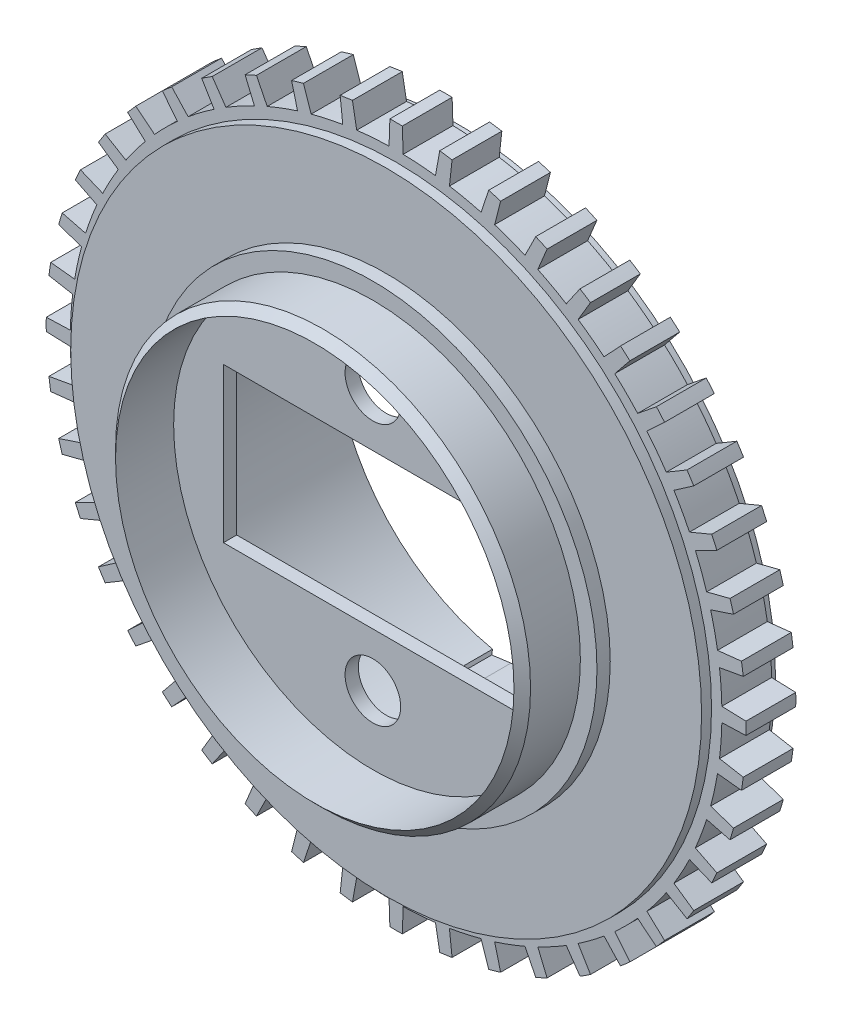
SolidWorks part; units mm, degrees
material "ABS"
ref_plane "Alzado" through (0, 0, 0) normal (0, 0, 1) x (1, 0, 0)
ref_plane "Planta" through (0, 0, 0) normal (0, 1, 0) x (1, 0, 0)
ref_plane "Vista lateral" through (0, 0, 0) normal (1, 0, 0) x (0, 0, -1)
sketch "Croquis1" plane through (0, 0, 0) normal (0, 0, 1) x (1, 0, 0)
  line L0 (0, 0) -> (0, 14.5885) construction
  line L1 (-0.375, 21.0712) -> (-0.425, 19.62)
  line L2 (0.375, 21.0712) -> (0.425, 19.62)
  line L3 (3.3699, 20.8034) -> (3.2129, 19.3598)
  line L4 (2.6276, 20.9101) -> (2.3715, 19.4807)
  line L5 (6.2963, 20.112) -> (5.9354, 18.7055)
  line L6 (5.5766, 20.3233) -> (5.1198, 18.9449)
  line L7 (9.0944, 19.0113) -> (8.537, 17.6704)
  line L8 (8.4122, 19.3228) -> (7.7638, 18.0235)
  line L9 (11.7074, 17.5235) -> (10.9649, 16.2756)
  line L10 (11.0765, 17.929) -> (10.2498, 16.7351)
  line L11 (14.0821, 15.679) -> (13.1695, 14.5495)
  line L12 (13.5153, 16.1701) -> (12.5271, 15.1061)
  line L13 (16.1701, 13.5153) -> (15.1061, 12.5271)
  line L14 (15.679, 14.0821) -> (14.5495, 13.1695)
  line L15 (17.929, 11.0765) -> (16.7351, 10.2498)
  line L16 (17.5235, 11.7074) -> (16.2756, 10.9649)
  line L17 (19.3228, 8.4122) -> (18.0235, 7.7638)
  line L18 (19.0113, 9.0944) -> (17.6704, 8.537)
  line L19 (20.3233, 5.5766) -> (18.9449, 5.1198)
  line L20 (20.112, 6.2963) -> (18.7055, 5.9354)
  line L21 (20.9101, 2.6276) -> (19.4807, 2.3715)
  line L22 (20.8034, 3.3699) -> (19.3598, 3.2129)
  line L23 (21.0712, -0.375) -> (19.62, -0.425)
  line L24 (21.0712, 0.375) -> (19.62, 0.425)
  line L25 (20.8034, -3.3699) -> (19.3598, -3.2129)
  line L26 (20.9101, -2.6276) -> (19.4807, -2.3715)
  line L27 (20.112, -6.2963) -> (18.7055, -5.9354)
  line L28 (20.3233, -5.5766) -> (18.9449, -5.1198)
  line L29 (19.0113, -9.0944) -> (17.6704, -8.537)
  line L30 (19.3228, -8.4122) -> (18.0235, -7.7638)
  line L31 (17.5235, -11.7074) -> (16.2756, -10.9649)
  line L32 (17.929, -11.0765) -> (16.7351, -10.2498)
  line L33 (15.679, -14.0821) -> (14.5495, -13.1695)
  line L34 (16.1701, -13.5153) -> (15.1061, -12.5271)
  line L35 (13.5153, -16.1701) -> (12.5271, -15.1061)
  line L36 (14.0821, -15.679) -> (13.1695, -14.5495)
  line L37 (11.0765, -17.929) -> (10.2498, -16.7351)
  line L38 (11.7074, -17.5235) -> (10.9649, -16.2756)
  line L39 (8.4122, -19.3228) -> (7.7638, -18.0235)
  line L40 (9.0944, -19.0113) -> (8.537, -17.6704)
  line L41 (5.5766, -20.3233) -> (5.1198, -18.9449)
  line L42 (6.2963, -20.112) -> (5.9354, -18.7055)
  line L43 (2.6276, -20.9101) -> (2.3715, -19.4807)
  line L44 (3.3699, -20.8034) -> (3.2129, -19.3598)
  line L45 (-0.375, -21.0712) -> (-0.425, -19.62)
  line L46 (0.375, -21.0712) -> (0.425, -19.62)
  line L47 (-3.3699, -20.8034) -> (-3.2129, -19.3598)
  line L48 (-2.6276, -20.9101) -> (-2.3715, -19.4807)
  line L49 (-6.2963, -20.112) -> (-5.9354, -18.7055)
  line L50 (-5.5766, -20.3233) -> (-5.1198, -18.9449)
  line L51 (-9.0944, -19.0113) -> (-8.537, -17.6704)
  line L52 (-8.4122, -19.3228) -> (-7.7638, -18.0235)
  line L53 (-11.7074, -17.5235) -> (-10.9649, -16.2756)
  line L54 (-11.0765, -17.929) -> (-10.2498, -16.7351)
  line L55 (-14.0821, -15.679) -> (-13.1695, -14.5495)
  line L56 (-13.5153, -16.1701) -> (-12.5271, -15.1061)
  line L57 (-16.1701, -13.5153) -> (-15.1061, -12.5271)
  line L58 (-15.679, -14.0821) -> (-14.5495, -13.1695)
  line L59 (-17.929, -11.0765) -> (-16.7351, -10.2498)
  line L60 (-17.5235, -11.7074) -> (-16.2756, -10.9649)
  line L61 (-19.3228, -8.4122) -> (-18.0235, -7.7638)
  line L62 (-19.0113, -9.0944) -> (-17.6704, -8.537)
  line L63 (-20.3233, -5.5766) -> (-18.9449, -5.1198)
  line L64 (-20.112, -6.2963) -> (-18.7055, -5.9354)
  line L65 (-20.9101, -2.6276) -> (-19.4807, -2.3715)
  line L66 (-20.8034, -3.3699) -> (-19.3598, -3.2129)
  line L67 (-21.0712, 0.375) -> (-19.62, 0.425)
  line L68 (-21.0712, -0.375) -> (-19.62, -0.425)
  line L69 (-20.8034, 3.3699) -> (-19.3598, 3.2129)
  line L70 (-20.9101, 2.6276) -> (-19.4807, 2.3715)
  line L71 (-20.112, 6.2963) -> (-18.7055, 5.9354)
  line L72 (-20.3233, 5.5766) -> (-18.9449, 5.1198)
  line L73 (-19.0113, 9.0944) -> (-17.6704, 8.537)
  line L74 (-19.3228, 8.4122) -> (-18.0235, 7.7638)
  line L75 (-19.3228, 8.4122) -> (-19.0113, 9.0944)
  line L76 (-17.5235, 11.7074) -> (-16.2756, 10.9649)
  line L77 (-17.929, 11.0765) -> (-16.7351, 10.2498)
  line L78 (-15.679, 14.0821) -> (-14.5495, 13.1695)
  line L79 (-16.1701, 13.5153) -> (-15.1061, 12.5271)
  line L80 (-13.5153, 16.1701) -> (-12.5271, 15.1061)
  line L81 (-14.0821, 15.679) -> (-13.1695, 14.5495)
  line L82 (-11.0765, 17.929) -> (-10.2498, 16.7351)
  line L83 (-11.7074, 17.5235) -> (-10.9649, 16.2756)
  line L84 (-8.4122, 19.3228) -> (-7.7638, 18.0235)
  line L85 (-9.0944, 19.0113) -> (-8.537, 17.6704)
  line L86 (-5.5766, 20.3233) -> (-5.1198, 18.9449)
  line L87 (-6.2963, 20.112) -> (-5.9354, 18.7055)
  line L88 (-2.6276, 20.9101) -> (-2.3715, 19.4807)
  line L89 (-3.3699, 20.8034) -> (-3.2129, 19.3598)
  line L90 (-3.3699, 20.8034) -> (-2.6276, 20.9101)
  line L91 (-6.2963, 20.112) -> (-5.5766, 20.3233)
  line L92 (-9.0944, 19.0113) -> (-8.4122, 19.3228)
  line L93 (-11.7074, 17.5235) -> (-11.0765, 17.929)
  line L94 (-14.0821, 15.679) -> (-13.5153, 16.1701)
  line L95 (-16.1701, 13.5153) -> (-15.679, 14.0821)
  line L96 (-17.929, 11.0765) -> (-17.5235, 11.7074)
  arc A0 (-20.9101, -2.6276) -> (-20.8034, -3.3699) centre (0, 0) ccw
  arc A1 (2.3715, 19.4807) -> (0.425, 19.62) centre (0, 0) ccw
  arc A2 (-20.3233, -5.5766) -> (-20.112, -6.2963) centre (0, 0) ccw
  arc A3 (-19.3228, -8.4122) -> (-19.0113, -9.0944) centre (0, 0) ccw
  arc A4 (-17.929, -11.0765) -> (-17.5235, -11.7074) centre (0, 0) ccw
  arc A5 (-16.1701, -13.5153) -> (-15.679, -14.0821) centre (0, 0) ccw
  arc A6 (-14.0821, -15.679) -> (-13.5153, -16.1701) centre (0, 0) ccw
  arc A7 (-11.7074, -17.5235) -> (-11.0765, -17.929) centre (0, 0) ccw
  arc A8 (-9.0944, -19.0113) -> (-8.4122, -19.3228) centre (0, 0) ccw
  arc A9 (-6.2963, -20.112) -> (-5.5766, -20.3233) centre (0, 0) ccw
  arc A10 (-3.3699, -20.8034) -> (-2.6276, -20.9101) centre (0, 0) ccw
  arc A11 (3.3699, 20.8034) -> (2.6276, 20.9101) centre (0, 0) ccw
  arc A12 (0.375, 21.0712) -> (-0.375, 21.0712) centre (0, 0) ccw
  arc A13 (-20.8034, 3.3699) -> (-20.9101, 2.6276) centre (0, 0) ccw
  arc A14 (-21.0712, 0.375) -> (-21.0712, -0.375) centre (0, 0) ccw
  arc A15 (-20.112, 6.2963) -> (-20.3233, 5.5766) centre (0, 0) ccw
  arc A16 (6.2963, 20.112) -> (5.5766, 20.3233) centre (0, 0) ccw
  arc A17 (9.0944, 19.0113) -> (8.4122, 19.3228) centre (0, 0) ccw
  arc A18 (11.7074, 17.5235) -> (11.0765, 17.929) centre (0, 0) ccw
  arc A19 (14.0821, 15.679) -> (13.5153, 16.1701) centre (0, 0) ccw
  arc A20 (16.1701, 13.5153) -> (15.679, 14.0821) centre (0, 0) ccw
  arc A21 (17.929, 11.0765) -> (17.5235, 11.7074) centre (0, 0) ccw
  arc A22 (19.3228, 8.4122) -> (19.0113, 9.0944) centre (0, 0) ccw
  arc A23 (20.3233, 5.5766) -> (20.112, 6.2963) centre (0, 0) ccw
  arc A24 (20.9101, 2.6276) -> (20.8034, 3.3699) centre (0, 0) ccw
  arc A25 (21.0712, -0.375) -> (21.0712, 0.375) centre (0, 0) ccw
  arc A26 (17.5235, -11.7074) -> (17.929, -11.0765) centre (0, 0) ccw
  arc A27 (15.679, -14.0821) -> (16.1701, -13.5153) centre (0, 0) ccw
  arc A28 (13.5153, -16.1701) -> (14.0821, -15.679) centre (0, 0) ccw
  arc A29 (8.4122, -19.3228) -> (9.0944, -19.0113) centre (0, 0) ccw
  arc A30 (5.5766, -20.3233) -> (6.2963, -20.112) centre (0, 0) ccw
  arc A31 (2.6276, -20.9101) -> (3.3699, -20.8034) centre (0, 0) ccw
  arc A32 (-0.375, -21.0712) -> (0.375, -21.0712) centre (0, 0) ccw
  arc A33 (19.0113, -9.0944) -> (19.3228, -8.4122) centre (0, 0) ccw
  arc A34 (20.112, -6.2963) -> (20.3233, -5.5766) centre (0, 0) ccw
  arc A35 (20.8034, -3.3699) -> (20.9101, -2.6276) centre (0, 0) ccw
  arc A36 (5.1198, 18.9449) -> (3.2129, 19.3598) centre (0, 0) ccw
  arc A37 (7.7638, 18.0235) -> (5.9354, 18.7055) centre (0, 0) ccw
  arc A38 (-18.9449, 5.1198) -> (-19.3598, 3.2129) centre (0, 0) ccw
  arc A39 (-0.425, 19.62) -> (-2.3715, 19.4807) centre (0, 0) ccw
  arc A40 (-19.4807, 2.3715) -> (-19.62, 0.425) centre (0, 0) ccw
  arc A41 (-19.62, -0.425) -> (-19.4807, -2.3715) centre (0, 0) ccw
  arc A42 (-19.3598, -3.2129) -> (-18.9449, -5.1198) centre (0, 0) ccw
  arc A43 (10.2498, 16.7351) -> (8.537, 17.6704) centre (0, 0) ccw
  arc A44 (12.5271, 15.1061) -> (10.9649, 16.2756) centre (0, 0) ccw
  arc A45 (14.5495, 13.1695) -> (13.1695, 14.5495) centre (0, 0) ccw
  arc A46 (16.2756, 10.9649) -> (15.1061, 12.5271) centre (0, 0) ccw
  arc A47 (17.6704, 8.537) -> (16.7351, 10.2498) centre (0, 0) ccw
  arc A48 (18.7055, 5.9354) -> (18.0235, 7.7638) centre (0, 0) ccw
  arc A49 (19.3598, 3.2129) -> (18.9449, 5.1198) centre (0, 0) ccw
  arc A50 (19.62, 0.425) -> (19.4807, 2.3715) centre (0, 0) ccw
  arc A51 (19.4807, -2.3715) -> (19.62, -0.425) centre (0, 0) ccw
  arc A52 (18.9449, -5.1198) -> (19.3598, -3.2129) centre (0, 0) ccw
  arc A53 (18.0235, -7.7638) -> (18.7055, -5.9354) centre (0, 0) ccw
  arc A54 (16.7351, -10.2498) -> (17.6704, -8.537) centre (0, 0) ccw
  arc A55 (15.1061, -12.5271) -> (16.2756, -10.9649) centre (0, 0) ccw
  arc A56 (13.1695, -14.5495) -> (14.5495, -13.1695) centre (0, 0) ccw
  arc A57 (10.9649, -16.2756) -> (12.5271, -15.1061) centre (0, 0) ccw
  arc A58 (8.537, -17.6704) -> (10.2498, -16.7351) centre (0, 0) ccw
  arc A59 (5.9354, -18.7055) -> (7.7638, -18.0235) centre (0, 0) ccw
  arc A60 (3.2129, -19.3598) -> (5.1198, -18.9449) centre (0, 0) ccw
  arc A61 (0.425, -19.62) -> (2.3715, -19.4807) centre (0, 0) ccw
  arc A62 (-2.3715, -19.4807) -> (-0.425, -19.62) centre (0, 0) ccw
  arc A63 (-5.1198, -18.9449) -> (-3.2129, -19.3598) centre (0, 0) ccw
  arc A64 (-7.7638, -18.0235) -> (-5.9354, -18.7055) centre (0, 0) ccw
  arc A65 (-10.2498, -16.7351) -> (-8.537, -17.6704) centre (0, 0) ccw
  arc A66 (-12.5271, -15.1061) -> (-10.9649, -16.2756) centre (0, 0) ccw
  arc A67 (-14.5495, -13.1695) -> (-13.1695, -14.5495) centre (0, 0) ccw
  arc A68 (-16.2756, -10.9649) -> (-15.1061, -12.5271) centre (0, 0) ccw
  arc A69 (-17.6704, -8.537) -> (-16.7351, -10.2498) centre (0, 0) ccw
  arc A70 (-18.7055, -5.9354) -> (-18.0235, -7.7638) centre (0, 0) ccw
  arc A71 (11.0765, -17.929) -> (11.7074, -17.5235) centre (0, 0) ccw
  circle A72 centre (0, 0) radius 12
  arc A73 (-18.0235, 7.7638) -> (-18.7055, 5.9354) centre (0, 0) ccw
  arc A74 (-16.7351, 10.2498) -> (-17.6704, 8.537) centre (0, 0) ccw
  arc A75 (-15.1061, 12.5271) -> (-16.2756, 10.9649) centre (0, 0) ccw
  arc A76 (-13.1695, 14.5495) -> (-14.5495, 13.1695) centre (0, 0) ccw
  arc A77 (-10.9649, 16.2756) -> (-12.5271, 15.1061) centre (0, 0) ccw
  arc A78 (-8.537, 17.6704) -> (-10.2498, 16.7351) centre (0, 0) ccw
  arc A79 (-5.9354, 18.7055) -> (-7.7638, 18.0235) centre (0, 0) ccw
  arc A80 (-3.2129, 19.3598) -> (-5.1198, 18.9449) centre (0, 0) ccw
  point P151 (0, 0)
  point P181 (-1.4, 19.5746)
  point P182 (1.4, 19.5746)
  dimension "D1" = 1.45
  dimension "D6" = 24
  dimension "D2" = 0.85
  dimension "D3" = 0.75
  dimension "D5" = 2.8
  dimension "D4" = 44
extrude "Saliente-Extruir1" add sketch "Croquis1" along normal blind 3
sketch "Croquis2" plane through (0, 0, 3) normal (0, 0, 1) x (1, 0, 0)
  circle A0 centre (0, 0) radius 19
  circle A1 centre (0, 0) radius 12
  circle A2 centre (0, 0) radius 12 construction
  dimension "D1" = 38
extrude "Saliente-Extruir2" add sketch "Croquis2" along normal blind 0.6
sketch "Croquis3" plane through (0, 0, 3.6) normal (0, 0, 1) x (1, 0, 0)
  circle A0 centre (0, 0) radius 12
  circle A1 centre (0, 0) radius 12.5
  circle A3 centre (0, 0) radius 12 construction
  dimension "D1" = 25
sketch "Croquis4" plane through (0, 0, 0) normal (0, 0, -1) x (-1, 0, 0)
  circle A0 centre (0, 0) radius 12
  circle A1 centre (0, 0) radius 12.45
  circle A2 centre (0, 0) radius 12 construction
  dimension "D1" = 24.9
extrude "Saliente-Extruir4" add sketch "Croquis4" along normal blind 5.8
sketch "Croquis6" plane through (0, 0, 0) normal (0, 0, -1) x (-1, 0, 0)
  circle A0 centre (0, 0) radius 19.25
  circle A1 centre (0, 0) radius 12
  circle A2 centre (0, 0) radius 12 construction
  dimension "D1" = 38.5
extrude "Saliente-Extruir6" add sketch "Croquis6" along normal blind 0.6
sketch "Croquis5" plane through (0, 0, -0.6) normal (0, 0, -1) x (-1, 0, 0)
  circle A0 centre (0, 0) radius 12
  circle A1 centre (0, 0) radius 13.5
  circle A2 centre (0, 0) radius 12 construction
  dimension "D1" = 27
extrude "Saliente-Extruir5" add sketch "Croquis5" along normal blind 0.6
chamfer "Chaflán2" distance 0.8 angle 60 rebuild error yes
extrude "Saliente-Extruir7" add sketch "Croquis3" along normal blind 4.8
chamfer "Chaflán4" distance 1 angle 45 2 edges at (-12.45, 0, -5.8) (12.5, 0, 8.4)
sketch "Croquis7" plane through (0, 0, 3.6) normal (0, 0, 1) x (1, 0, 0)
  circle A0 centre (0, 0) radius 2
  circle A1 centre (0, 0) radius 13.5
  circle A2 centre (0, 0) radius 2 construction
  dimension "D1" = 27
extrude "Saliente-Extruir8" add sketch "Croquis7" along normal blind 0.8
sketch "Croquis8" plane through (0, 0, 0) normal (0, 0, 1) x (1, 0, 0)
  line L0 (0, 0) -> (6.706, 0) construction
  line L1 (-8, 3.5) -> (8, 3.5)
  line L2 (-8, 3.5) -> (-8, -3.5)
  line L3 (-8, -3.5) -> (8, -3.5)
  line L4 (8, 3.5) -> (8, -3.5)
  line L5 (-8, 3.5) -> (8, -3.5) construction
  line L6 (-8, -3.5) -> (8, 3.5) construction
  circle A0 centre (0, 7.8756) radius 1.675
  circle A1 centre (0, -7.8756) radius 1.675
  point P0 (0, 0)
  dimension "D1" = 3.35
  dimension "D2" = 7
  dimension "D3" = 16
extrude "Cortar-Extruir1" cut sketch "Croquis8" against normal through all both and the other way through all
sketch "Croquis9" plane through (0, 0, -5.8) normal (0, 0, -1) x (-1, 0, 0)
  line L1 (2.3383, 3.8256) -> (4.6765, 7.8756)
  line L2 (4.6765, 7.8756) -> (2.3383, 11.9256)
  line L3 (2.3383, 11.9256) -> (-2.3383, 11.9256)
  line L4 (-2.3383, 11.9256) -> (-4.6765, 7.8756)
  line L5 (-4.6765, 7.8756) -> (-2.3383, 3.8256)
  line L6 (-2.3383, 3.8256) -> (2.3383, 3.8256)
  line L7 (2.3383, -11.9256) -> (4.6765, -7.8756)
  line L8 (4.6765, -7.8756) -> (2.3383, -3.8256)
  line L9 (2.3383, -3.8256) -> (-2.3383, -3.8256)
  line L10 (-2.3383, -3.8256) -> (-4.6765, -7.8756)
  line L11 (-4.6765, -7.8756) -> (-2.3383, -11.9256)
  line L12 (-2.3383, -11.9256) -> (2.3383, -11.9256)
  circle A0 centre (0, 7.8756) radius 4.05 construction
  circle A1 centre (0, -7.8756) radius 4.05 construction
  dimension "D1" = 8.1
extrude "Cortar-Extruir2" cut sketch "Croquis9" against normal blind 4
fillet "Redondeo1" radius 2.5 rebuild error yes
sketch "Croquis10" plane through (0, 0, 12.6) normal (0, 0, 1) x (1, 0, 0)
  line L1 (9, 4.65) -> (-9, 4.65)
  line L2 (9, 4.65) -> (9, -4.65)
  line L3 (9, -4.65) -> (-9, -4.65)
  line L4 (-9, 4.65) -> (-9, -4.65)
  line L5 (9, 4.65) -> (-9, -4.65) construction
  line L6 (9, -4.65) -> (-9, 4.65) construction
  point P0 (0, 0)
  dimension "D1" = 9.3
  dimension "D2" = 18
extrude "Cortar-Extruir3" cut sketch "Croquis10" against normal blind 9
chamfer "Chaflán5" distance 1 angle 45 rebuild error yes
